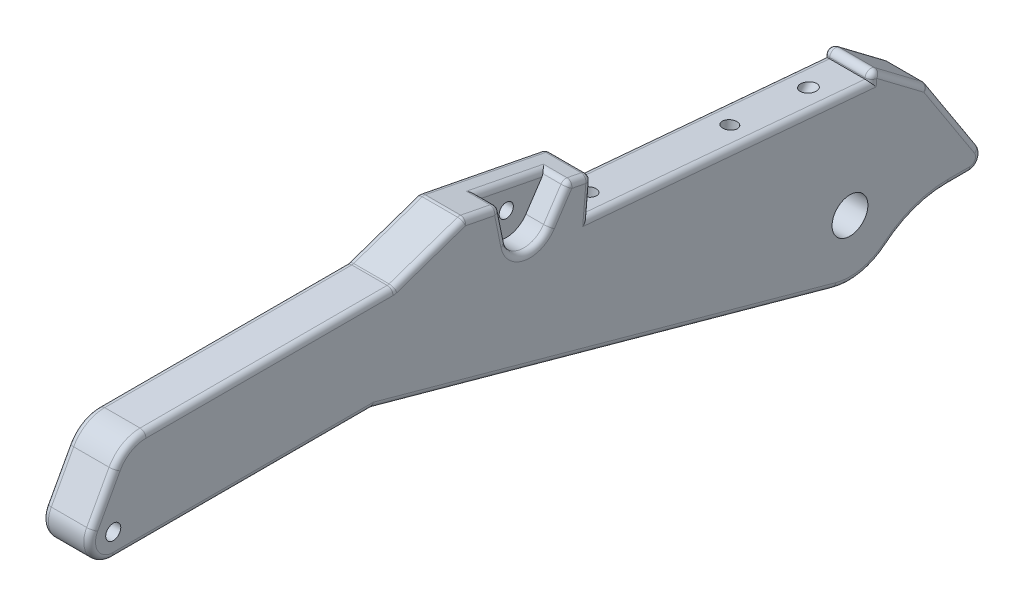
SolidWorks part; units mm, degrees
ref_plane "Front Plane" through (0, 0, 0) normal (0, 0, 1) x (1, 0, 0)
ref_plane "Top Plane" through (0, 0, 0) normal (0, 1, 0) x (1, 0, 0)
ref_plane "Right Plane" through (0, 0, 0) normal (1, 0, 0) x (0, 0, -1)
sketch "Sketch1" plane through (0, 0, 0) normal (1, 0, 0) x (0, 0, -1)
  line L0 (-5.5746, 3.0408) -> (3.158, 19.05)
  line L1 (3.158, 19.05) -> (75.6627, 19.05)
  line L3 (129.0542, 18.9233) -> (128.2241, 9.4345)
  line L4 (128.2241, 9.4345) -> (204.1341, 2.7933)
  line L6 (0, -6.35) -> (69.85, -6.35)
  line L8 (-5.5746, 3.0408) -> (7.9306, 27.7995) construction
  line L9 (129.0542, 18.9233) -> (94.7762, 25.6144)
  line L10 (94.7762, 25.6144) -> (75.6627, 19.05)
  line L11 (129.0542, 18.9233) -> (128.2241, 9.4345) construction
  line L12 (70.0006, 30.4506) -> (127.6524, 19.1969) construction
  line L24 (219.6164, -5.5196) -> (233.4447, -26.8477) construction
  line L26 (219.7687, -5.7545) -> (233.4447, -26.8477)
  line L29 (69.85, 30.48) -> (129.0542, 18.9233) construction
  line L30 (206.6988, 4.2294) -> (219.393, -5.351) construction
  line L31 (204.1341, 2.7933) -> (204.161, 3.1007) construction
  line L32 (230.7807, -31.75) -> (224.8967, -31.75) construction
  line L33 (194.299, -40.7027) -> (69.85, -6.35) construction
  line L34 (206.6988, 4.2294) -> (219.393, -5.351)
  line L35 (204.1341, 2.7933) -> (204.161, 3.1007)
  line L36 (230.7807, -31.75) -> (224.8967, -31.75)
  line L37 (194.299, -40.7027) -> (69.85, -6.35)
  line L39 (-5.5746, 3.0408) -> (7.9306, 27.7995) construction
  circle A0 centre (0, 0) radius 2.032
  arc A1 (-5.5746, 3.0408) -> (0, -6.35) centre (0, 0) ccw
  arc A3 (0, -6.35) -> (-5.5746, 3.0408) centre (0, 0) ccw construction
  arc A12 (230.7807, -31.75) -> (233.4447, -26.8477) centre (230.7807, -28.575) ccw construction
  arc A13 (230.7807, -31.75) -> (233.4447, -26.8477) centre (230.7807, -28.575) ccw
  arc A14 (206.6988, 4.2294) -> (204.161, 3.1007) centre (205.7425, 2.9623) ccw construction
  arc A15 (224.8967, -31.75) -> (208.6668, -37.6115) centre (224.8967, -57.15) ccw construction
  arc A16 (194.299, -40.7027) -> (208.6668, -37.6115) centre (198.5232, -25.4) ccw construction
  arc A17 (206.6988, 4.2294) -> (204.161, 3.1007) centre (205.7425, 2.9623) ccw
  arc A18 (224.8967, -31.75) -> (208.6668, -37.6115) centre (224.8967, -57.15) ccw
  arc A19 (194.299, -40.7027) -> (208.6668, -37.6115) centre (198.5232, -25.4) ccw
  arc A20 (219.7687, -5.7545) -> (219.393, -5.351) centre (218.4366, -6.6181) ccw construction
  arc A21 (219.7687, -5.7545) -> (219.393, -5.351) centre (218.4366, -6.6181) ccw
  dimension "D1" = 4.064
  dimension "D2" = 19.05
  dimension "D3" = 30
  dimension "D4" = 34.925
extrude "Boss-Extrude1" add sketch "Sketch1" along normal blind 12.7
fillet "Fillet1" radius 9.525 1 edges at (6.35, 19.05, -3.158)
sketch "Sketch2" plane through (0, 0, 0) normal (-1, 0, 0) x (0, 0, 1)
  circle A0 centre (-198.5232, -25.4) radius 4.826
  circle A3 centre (-198.5232, -25.4) radius 5.715 construction
  dimension "D1" = 9.652
extrude "Cut-Extrude1" cut sketch "Sketch2" against normal through all
sketch "Sketch9" plane through (12.7, 0, 0) normal (1, 0, 0) x (0, 0, -1)
  line L0 (106.0359, 14.4582) -> (104.1247, 23.7895)
  line L2 (117.5418, 12.2123) -> (122.8219, 20.1398)
  line L3 (104.1247, 23.7895) -> (122.8219, 20.1398)
  line L4 (129.0542, 18.9233) -> (94.7762, 25.6144) construction
  arc A0 (106.0359, 14.4582) -> (117.5418, 12.2123) centre (112.2567, 15.7323) ccw
  dimension "D1" = 12.7
  dimension "D2" = 6.35
  dimension "D3" = 19.05
extrude "Cut-Extrude6" cut sketch "Sketch9" against normal blind 6.35
sketch "Sketch10" plane through (6.35, 0, 0) normal (1, 0, 0) x (0, 0, -1)
  circle A0 centre (112.2567, 15.7323) radius 1.905
  arc A1 (106.0359, 14.4582) -> (117.5418, 12.2123) centre (112.2567, 15.7323) ccw construction
  dimension "D1" = 3.81
extrude "Cut-Extrude7" cut sketch "Sketch10" against normal through all
sketch "Sketch4" plane through (0, 0, 0) normal (1, 0, 0) x (0, 0, -1)
  circle A0 centre (198.5232, -25.4) radius 5.715
  dimension "D1" = 11.43
extrude "Cut-Extrude2" cut sketch "Sketch4" along normal blind 1.5875
fillet "Fillet2" radius 1.5875 48 edges at (0, 2.947, -204.1476) (0, 4.4128, -205.0973) (0, -0.5608, -213.0459) (0, -5.5363, -219.5985) (0, -16.3011, -226.6067) (0, -30.091, -233.5704) (0, -31.75, -227.8387) (0, -33.2603, -216.2687) (0, -40.9199, -201.8622) (0, -6.35, -34.925) (0, -3.2414, 5.4604) (0, 8.5635, 2.5621) (0, 17.7156, -3.9501) (12.7, 2.947, -204.1476) (12.7, 4.4128, -205.0973) (12.7, -0.5608, -213.0459) (12.7, -5.5363, -219.5985) (12.7, -16.3011, -226.6067) (12.7, -30.091, -233.5704) (12.7, -31.75, -227.8387) (12.7, -33.2603, -216.2687) (12.7, -40.9199, -201.8622) (12.7, -6.35, -34.925) (12.7, -3.2414, 5.4604) (12.7, 8.5635, 2.5621) (12.7, 17.7156, -3.9501) (0, -23.5263, -132.0745) (0, 6.1139, -166.1791) (0, 14.1789, -128.6392) (0, 19.05, -42.2375) (12.7, -23.5263, -132.0745) (12.7, 6.1139, -166.1791) (12.7, 14.1789, -128.6392) (12.7, 19.05, -42.2375) (12.7, 19.1239, -105.0803) (12.7, 16.1761, -120.1818) (12.7, 9.4999, -111.0402) (12.7, 19.5316, -125.938) (0, 22.2688, -111.9152) (9.525, 20.1398, -122.8219) (9.525, 23.7895, -104.1247) (6.35, 21.9647, -113.4733) (12.7, 24.702, -99.4505) (12.7, 22.3322, -85.2195) (0, 22.3322, -85.2195) (6.35, 25.6144, -94.7762) (6.35, 19.05, -75.6627) (6.35, 18.9233, -129.0542)
sketch "Sketch6" plane through (0, 102.0823, -77.0424) normal (0, 0.7982, -0.6024) x (1, 0, 0)
  circle A0 centre (6.35, 152.3647) radius 1.905
  circle A1 centre (6.35, 152.3647) radius 2.286 construction
  dimension "D1" = 3.81
extrude "Cut-Extrude3" cut sketch "Sketch6" against normal blind 25.4
sketch "Sketch7" plane through (0, 20.4958, -1.7931) normal (0, 0.9962, -0.0872) x (1, 0, 0)
  circle A0 centre (6.35, 171.3639) radius 1.905
  circle A1 centre (6.35, 133.2639) radius 1.905
  circle A2 centre (6.35, 133.2639) radius 2.286 construction
  circle A3 centre (6.35, 171.3639) radius 2.286 construction
  dimension "D1" = 3.81
extrude "Cut-Extrude4" cut sketch "Sketch7" against normal blind 15.875
sketch "Sketch8" plane through (0, 98.6153, -152.0993) normal (0, 0.544, -0.8391) x (-1, 0, 0)
  circle A0 centre (-6.35, -139.9823) radius 1.905
  circle A1 centre (-6.35, -139.9823) radius 2.286 construction
  dimension "D1" = 3.81
extrude "Cut-Extrude5" cut sketch "Sketch8" against normal blind 12.7
